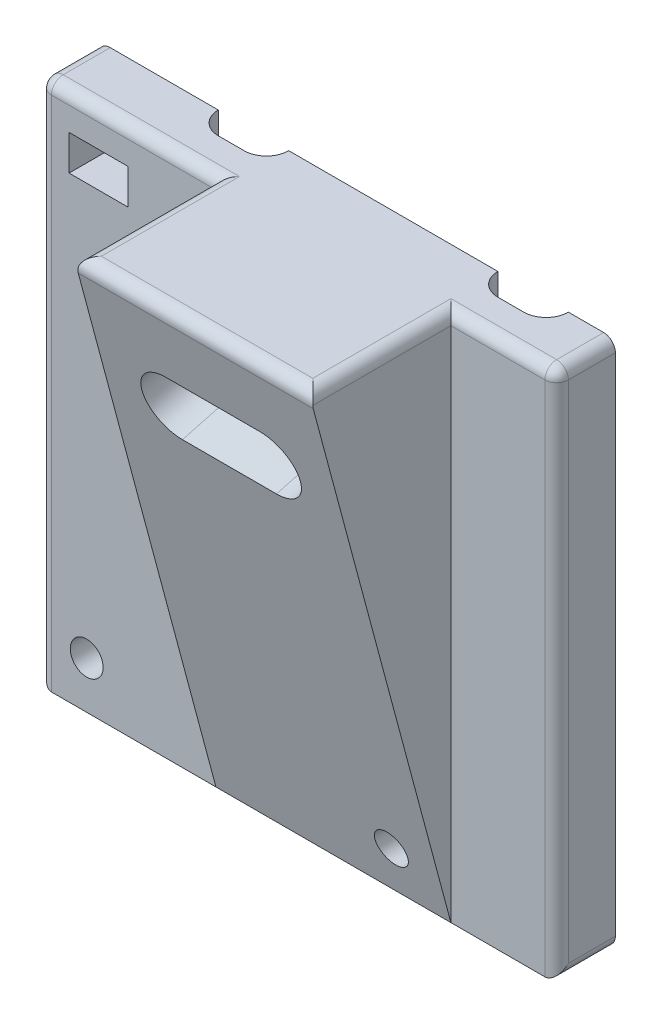
SolidWorks part; units mm, degrees
ref_plane "Front Plane" through (0, 0, 0) normal (0, 0, 1) x (1, 0, 0)
ref_plane "Top Plane" through (0, 0, 0) normal (0, 1, 0) x (1, 0, 0)
ref_plane "Right Plane" through (0, 0, 0) normal (1, 0, 0) x (0, 0, -1)
sketch "Sketch1" plane through (0, 0, 0) normal (0, 0, 1) x (1, 0, 0)
  line L1 (-22, 22.5) -> (22, 22.5)
  line L2 (-22, 22.5) -> (-22, -22.5)
  line L3 (-22, -22.5) -> (22, -22.5)
  line L4 (22, 22.5) -> (22, -22.5)
  line L5 (-22, 22.5) -> (22, -22.5) construction
  line L6 (-22, -22.5) -> (22, 22.5) construction
  point P0 (0, 0)
  dimension "D1" = 44
  dimension "D2" = 45
extrude "Base" add sketch "Sketch1" along normal blind 5
sketch "Sketch2" plane through (0, 22.5, 0) normal (0, 1, 0) x (1, 0, 0)
  line L0 (22, 0) -> (-22, 0) construction
  line L1 (12, 0) -> (18, 0)
  line L2 (12, 0) -> (12, -5) construction
  line L3 (22, -5) -> (-22, -5) construction
  line L5 (13.9, -1.9) -> (16.1, -1.9)
  line L6 (3.1, 0) -> (3.1, -5) construction
  line L7 (-7.7, -1.9) -> (-9.9, -1.9)
  line L8 (-5.8, 0) -> (-11.8, 0)
  arc A1 (12, 0) -> (13.9, -1.9) centre (13.9, 0) ccw
  arc A2 (16.1, -1.9) -> (18, 0) centre (16.1, 0) ccw
  arc A3 (-5.8, 0) -> (-7.7, -1.9) centre (-7.7, 0) cw
  arc A4 (-9.9, -1.9) -> (-11.8, 0) centre (-9.9, 0) cw
  point P5 (15, 0)
  dimension "D1" = 15
  dimension "D2" = 6
  dimension "D3" = 1.9
  dimension "D4" = 11.9
extrude "Wire Grooves" cut sketch "Sketch2" against normal through all
sketch "Sketch4" plane through (22, 0, 0) normal (1, 0, 0) x (0, 0, -1)
  line L0 (-5, -22.5) -> (-5, 22.5)
  line L1 (-5, -22.5) -> (-17.0577, 22.5)
  line L2 (-17.0577, 22.5) -> (-5, 22.5)
  dimension "D1" = 15
extrude "Slanted Screw Platform" add sketch "Sketch4" against normal blind 7 and the other way blind 13 from surface starting at plane "Right Plane"
sketch "Sketch5" plane through (0, -2.7572, 10.2901) normal (0, -0.2588, 0.9659) x (1, 0, 0)
  line L0 (7, 16.5) -> (-1, 16.5) construction
  line L2 (7, 13.75) -> (-1, 13.75)
  line L3 (7, 19.25) -> (-1, 19.25)
  line L4 (3, 26.1482) -> (3, -20.4392) construction
  line L5 (13, 26.1482) -> (-7, 26.1482) construction
  line L6 (13, -20.4392) -> (-7, -20.4392) construction
  arc A1 (7, 13.75) -> (7, 19.25) centre (7, 16.5) ccw
  arc A2 (-1, 19.25) -> (-1, 13.75) centre (-1, 16.5) ccw
  point P2 (3, 16.5)
  point P15 (0, 0)
  point P16 (-6.4219, 16.5)
  dimension "D1" = 16.5
  dimension "D2" = 2.75
  dimension "D3" = 8
extrude "Mounting Hole Screw Insertion" cut sketch "Sketch5" against normal through all
sketch "Sketch6" plane through (0, 0, 5) normal (0, 0, 1) x (1, 0, 0)
  line L0 (3, 22.5) -> (3, -22.5) construction
  line L1 (-7, 22.5) -> (13, 22.5) construction
  line L2 (-7, -22.5) -> (13, -22.5) construction
  line L4 (-19.5, 19.5) -> (-14.5, 19.5)
  line L5 (-19.5, 19.5) -> (-19.5, 16.5)
  line L6 (-19.5, 16.5) -> (-14.5, 16.5)
  line L7 (-14.5, 19.5) -> (-14.5, 16.5)
  line L8 (-7, 22.5) -> (-22, 22.5) construction
  line L9 (-1, 22.5) -> (-1, -22.5) construction
  point P16 (-17, 16.5)
  dimension "D1" = 5
  dimension "D2" = 3
  dimension "D3" = 3
  dimension "D4" = 20
  dimension "D5" = 4
extrude "Zip Tie Slots" cut sketch "Sketch6" against normal through all
sketch "Sketch7" plane through (0, 0, 5) normal (0, 0, 1) x (1, 0, 0)
  line L0 (-22, 22.5) -> (-22, -22.5) construction
  line L1 (-22, -22.5) -> (-7, -22.5) construction
  line L2 (-4.5, 22.5) -> (-4.5, -22.5) construction
  line L5 (-7, 22.5) -> (13, 22.5) construction
  line L6 (-7, -22.5) -> (13, -22.5) construction
  circle A0 centre (-18, -18.5) radius 1.4
  circle A2 centre (9, -18.5) radius 1.4
  dimension "D1" = 2.8
  dimension "D2" = 4
  dimension "D3" = 4
  dimension "D4" = 4.5
extrude "Mount Clamping Holes" cut sketch "Sketch7" against normal through all both and the other way through all
fillet "Edge Fillets" radius 1 11 edges at (22, 0, 5) (-7, 22.5, 11.0289) (3, 22.5, 17.0577) (13, 22.5, 11.0289) (17.5, 22.5, 5) (-22, 0, 5) (-14.5, 22.5, 5) (22, -22.5, 2.5) (-22, -22.5, 2.5) (22, 22.5, 2.5) (-22, 22.5, 2.5)
